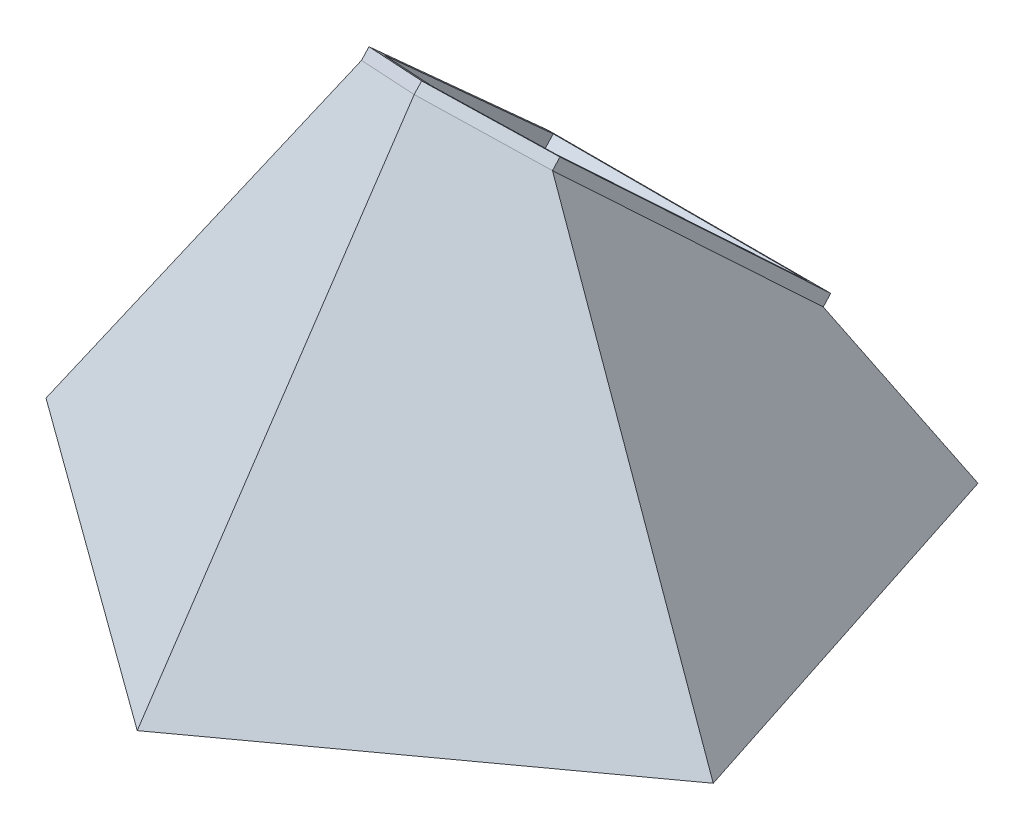
SolidWorks part; units mm, degrees
ref_plane "前视基准面" through (0, 0, 0) normal (0, 0, 1) x (1, 0, 0)
ref_plane "上视基准面" through (0, 0, 0) normal (0, 1, 0) x (1, 0, 0)
ref_plane "右视基准面" through (0, 0, 0) normal (1, 0, 0) x (0, 0, -1)
other "Configuration Table"
sketch "草图1" plane through (0, 0, 0) normal (0, 1, 0) x (1, 0, 0)
  line L1 (60.6763, -19.7149) -> (37.5, 51.6143)
  line L2 (37.5, 51.6143) -> (-37.5, 51.6143)
  line L3 (-37.5, 51.6143) -> (-60.6763, -19.7149)
  line L4 (-60.6763, -19.7149) -> (0, -63.7988)
  line L5 (0, -63.7988) -> (60.6763, -19.7149)
  circle A0 centre (0, 0) radius 51.6143 construction
  dimension "D1" = 75
ref_plane "基准面1" through (0, 95, 0) normal (0, 1, 0) x (1, 0, 0)
sketch "草图2" plane through (0, 95, 0) normal (0, 1, 0) x (1, 0, 0)
  point P0 (0, 0)
loft "放样1" add profiles "草图2", "草图1"
sketch "草图5" plane through (0, 0, 0) normal (1, 0, 0) x (0, 0, -1)
  line L0 (-13.4313, 75) -> (35.3151, 30)
  line L1 (0, 95) -> (-63.7988, 0) construction
  line L2 (0, 95) -> (51.6143, 0) construction
  line L3 (-63.7988, 0) -> (-19.7149, 0) construction
  line L4 (-19.7149, 0) -> (51.6143, 0) construction
  dimension "D1" = 75
  dimension "D2" = 30
extrude "切除-拉伸1" cut sketch "草图5" against normal through all both and the other way through all
sketch "草图8" plane through (0, 33.7982, -31.2006) normal (0, 0.7348, -0.6783) x (1, 0, 0)
  line L20 (15.5257, -48.9224) -> (23.3384, 3.5995)
  line L21 (0, -58.399) -> (15.5257, -48.9224)
  line L22 (-15.5257, -48.9224) -> (0, -58.399)
  line L23 (-23.3384, 3.5995) -> (-15.5257, -48.9224)
  line L24 (23.3384, 3.5995) -> (-23.3384, 3.5995)
  line L25 (15.5257, -48.9224) -> (23.3384, 3.5995)
  line L26 (0, -58.399) -> (15.5257, -48.9224)
  line L27 (-15.5257, -48.9224) -> (0, -58.399)
  line L28 (-23.3384, 3.5995) -> (-15.5257, -48.9224)
  line L29 (23.3384, 3.5995) -> (-23.3384, 3.5995)
  line L30 (-25.6579, 5.5995) -> (-17.3662, -50.142)
  line L31 (-17.3662, -50.142) -> (0, -60.7421)
  line L32 (0, -60.7421) -> (17.3662, -50.142)
  line L33 (17.3662, -50.142) -> (25.6579, 5.5995)
  line L34 (25.6579, 5.5995) -> (-25.6579, 5.5995)
  line L35 (-25.6579, 5.5995) -> (-17.3662, -50.142)
  line L36 (-17.3662, -50.142) -> (0, -60.7421)
  line L37 (0, -60.7421) -> (17.3662, -50.142)
  line L38 (17.3662, -50.142) -> (25.6579, 5.5995)
  line L39 (25.6579, 5.5995) -> (-25.6579, 5.5995)
  dimension "D1" = 2
  dimension "D2" = 0
extrude "凸台-拉伸3" add sketch "草图8" along normal blind 2
shell "抽壳2" thickness 2 removed face at (0, 0, 0)
sketch "草图9" plane through (0, 33.7982, -31.2006) normal (0, 0.7348, -0.6783) x (1, 0, 0)
  line L5 (0, -58.399) -> (15.5257, -48.9224)
  line L6 (15.5257, -48.9224) -> (23.3384, 3.5995)
  line L7 (23.3384, 3.5995) -> (-23.3384, 3.5995)
  line L8 (-23.3384, 3.5995) -> (-15.5257, -48.9224)
  line L9 (-15.5257, -48.9224) -> (0, -58.399)
  line L10 (0, -58.399) -> (15.5257, -48.9224)
  line L11 (15.5257, -48.9224) -> (23.3384, 3.5995)
  line L12 (23.3384, 3.5995) -> (-23.3384, 3.5995)
  line L13 (-23.3384, 3.5995) -> (-15.5257, -48.9224)
  line L14 (-15.5257, -48.9224) -> (0, -58.399)
  dimension "D1" = 0
extrude "切除-拉伸2" cut sketch "草图9" against normal blind 2
